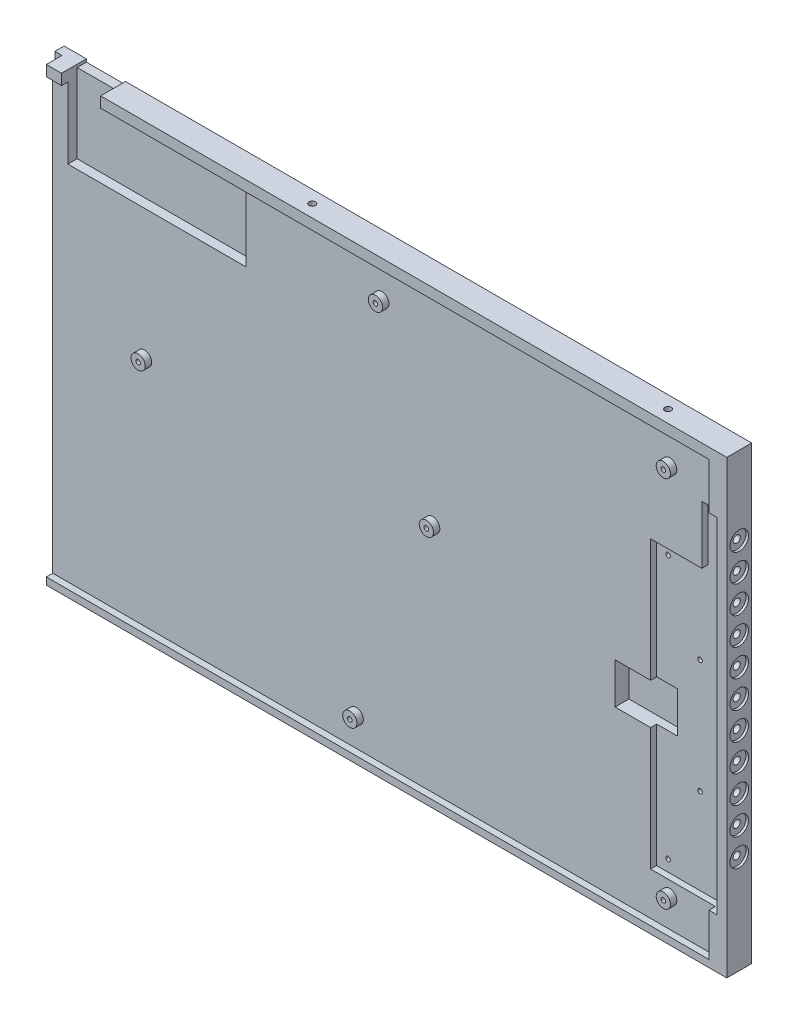
SolidWorks part; units mm, degrees
ref_plane "前视基准面" through (0, 0, 0) normal (0, 0, 1) x (1, 0, 0)
ref_plane "上视基准面" through (0, 0, 0) normal (0, 1, 0) x (1, 0, 0)
ref_plane "右视基准面" through (0, 0, 0) normal (1, 0, 0) x (0, 0, -1)
other "Configuration Table"
sketch "草图1" plane through (0, 0, 0) normal (0, 0, 1) x (1, 0, 0)
  line L1 (0, 0) -> (348.235, 0)
  line L2 (0, 0) -> (0, -124.71)
  line L3 (0, -124.71) -> (348.235, -124.71)
  line L4 (348.235, 0) -> (348.235, -124.71)
  dimension "D1" = 348.235
  dimension "D2" = 124.71
extrude "凸台-拉伸1" add sketch "草图1" along normal blind 7
sketch "草图2" plane through (0, 0, 7) normal (0, 0, 1) x (1, 0, 0)
  line L0 (348.235, 0) -> (0, 0) construction
  line L1 (2, -2) -> (346.235, -2)
  line L2 (2, -2) -> (2, -122.71)
  line L3 (2, -122.71) -> (346.235, -122.71)
  line L4 (346.235, -2) -> (346.235, -122.71)
  line L5 (348.235, -124.71) -> (348.235, 0) construction
  line L6 (0, -124.71) -> (348.235, -124.71) construction
  line L7 (0, 0) -> (0, -124.71) construction
  dimension "D1" = 2
  dimension "D2" = 2
  dimension "D3" = 2
  dimension "D4" = 2
extrude "切除-拉伸1" cut sketch "草图2" against normal blind 1.8
sketch "草图3" plane through (0, 0, 5.2) normal (0, 0, 1) x (1, 0, 0)
  circle A0 centre (4.8, -9.9) radius 2
  circle A1 centre (4.8, -9.9) radius 0.65
  circle A2 centre (7.2, -114.7) radius 2
  circle A3 centre (7.2, -114.7) radius 0.65
  circle A4 centre (76.2, -76.6) radius 2
  circle A5 centre (76.2, -76.6) radius 0.65
  circle A6 centre (128.6, -9.9) radius 2
  circle A7 centre (128.6, -9.9) radius 0.65
  circle A8 centre (126.3, -114.7) radius 2
  circle A9 centre (126.3, -114.7) radius 0.65
  circle A10 centre (185.8, -57.5) radius 2
  circle A11 centre (185.8, -57.5) radius 0.65
  circle A12 centre (252.5, -9.9) radius 2
  circle A13 centre (252.5, -9.9) radius 0.65
  circle A14 centre (245.3, -114.7) radius 2
  circle A15 centre (245.3, -114.7) radius 0.65
  circle A16 centre (333.4, -9.9) radius 2
  circle A17 centre (333.4, -9.9) radius 0.65
  circle A18 centre (333.4, -114.7) radius 2
  circle A19 centre (333.4, -114.7) radius 0.65
  circle A20 centre (266.8, -57.5) radius 2
  circle A21 centre (266.8, -57.5) radius 0.65
  dimension "D1" = 4
  dimension "D2" = 1.3
extrude "凸台-拉伸2" add sketch "草图3" along normal up to surface (1.8 mm away) up to face at (174.1175, -62.355, 7)
sketch "草图4" plane through (0, 0, 5.2) normal (0, 0, 1) x (1, 0, 0)
  line L0 (0, 0) -> (0, -124.71) construction
  line L1 (0, -27.51) -> (9.7, -27.51)
  line L2 (0, -27.51) -> (0, -107.91)
  line L3 (0, -107.91) -> (9.7, -107.91)
  line L4 (9.7, -27.51) -> (9.7, -107.91)
  line L5 (0, -124.71) -> (348.235, -124.71) construction
  dimension "D1" = 80.4
  dimension "D2" = 9.7
  dimension "D3" = 16.8
extrude "切除-拉伸2" cut sketch "草图4" against normal blind 1.7 and the other way through all contours L4 L3 L2 L1
sketch "草图6" plane through (0, 0, 5.2) normal (0, 0, 1) x (1, 0, 0)
  line L5 (3.9, -67.71) -> (9.7, -67.71) construction
  line L6 (3.9, -63.21) -> (19.7, -63.21)
  line L7 (3.9, -63.21) -> (3.9, -72.21)
  line L8 (3.9, -72.21) -> (19.7, -72.21)
  line L9 (19.7, -63.21) -> (19.7, -72.21)
  line L10 (9.7, -27.51) -> (9.7, -107.91) construction
  dimension "D1" = 9
  dimension "D2" = 5.8
  dimension "D3" = 10
extrude "切除-拉伸3" cut sketch "草图6" against normal offset from surface (3.9 mm away) 1.3 up to face at (174.1175, -62.355, 0)
sketch "草图7" plane through (0, 0, 0) normal (-1, 0, 0) x (0, 0, 1)
  line L1 (0, 0) -> (7, 0)
  line L2 (0, 0) -> (0, -27.51)
  line L3 (0, -27.51) -> (7, -27.51)
  line L4 (7, 0) -> (7, -27.51)
  line L5 (7, -107.91) -> (0, -107.91)
  line L6 (7, -107.91) -> (7, -124.71)
  line L7 (7, -124.71) -> (0, -124.71)
  line L8 (0, -107.91) -> (0, -124.71)
  line L9 (0, -107.91) -> (3.5, -107.91)
  line L10 (0, -107.91) -> (0, -27.51)
  line L11 (0, -27.51) -> (3.5, -27.51)
  line L12 (3.5, -107.91) -> (3.5, -27.51)
  line M1 (3.5, -107.91) -> (3.5, -27.51)
  line M2 (3.5, -27.51) -> (7, -27.51)
  line M3 (7, -27.51) -> (7, 0)
  line M4 (7, 0) -> (0, 0)
  line M5 (0, 0) -> (0, -124.71)
  line M6 (0, -124.71) -> (7, -124.71)
  line M7 (7, -124.71) -> (7, -107.91)
  line M8 (7, -107.91) -> (3.5, -107.91)
extrude "凸台-拉伸3" add sketch "草图7" along normal blind 11.7 contours L5 M8 M5 M6 M7 | L5 L3 M1 M5 | L3 M5 M2 M3 M4 region at (0, -13.755, 3.5) region at (0, -67.71, 1.75) region at (0, -116.31, 3.5)
sketch "草图8" plane through (0, 0, 3.5) normal (0, 0, 1) x (1, 0, 0)
  circle A0 centre (-5.5, -82.714) radius 0.7
  circle A1 centre (4.5, -102.714) radius 0.7
  circle A2 centre (-5.5, -52.714) radius 0.7
  circle A3 centre (4.5, -32.714) radius 0.7
  dimension "D1" = 1.4
extrude "切除-拉伸4" cut sketch "草图8" against normal blind 3
sketch "草图9" plane through (0, 0, 3.5) normal (0, 0, 1) x (1, 0, 0)
  line L0 (-11.7, -107.91) -> (2, -107.91) construction
  line L1 (-11.7, -27.51) -> (-10.7, -27.51)
  line L2 (-11.7, -27.51) -> (-11.7, -107.91)
  line L3 (-11.7, -107.91) -> (-10.7, -107.91)
  line L4 (-10.7, -27.51) -> (-10.7, -107.91)
  dimension "D1" = 1
extrude "凸台-拉伸4" add sketch "草图9" along normal up to surface (1.7 mm away) up to face at (64.8892, -65.925, 5.2)
sketch "草图10" plane through (0, 0, 5.2) normal (0, 0, 1) x (1, 0, 0)
  line L1 (328.035, -30.31) -> (348.235, -30.31)
  line L2 (328.035, -30.31) -> (328.035, -110.71)
  line L3 (328.035, -110.71) -> (348.235, -110.71)
  line L4 (348.235, -30.31) -> (348.235, -110.71)
  line L6 (348.235, -124.71) -> (348.235, 0) construction
  line L9 (2, -122.71) -> (346.235, -122.71) construction
  dimension "D1" = 80.4
  dimension "D2" = 20.2
  dimension "D3" = 12
extrude "切除-拉伸5" cut sketch "草图10" against normal blind 1.7 and the other way through all
sketch "草图11" plane through (0, 0, 3.5) normal (0, 0, 1) x (1, 0, 0)
  line L0 (328.035, -70.51) -> (333.835, -70.51) construction
  line L1 (318.035, -64.76) -> (333.835, -64.76)
  line L2 (318.035, -64.76) -> (318.035, -76.26)
  line L3 (318.035, -76.26) -> (333.835, -76.26)
  line L4 (333.835, -64.76) -> (333.835, -76.26)
  line L5 (328.035, -110.71) -> (328.035, -30.31) construction
  dimension "D1" = 11.5
  dimension "D2" = 5.8
  dimension "D3" = 10
extrude "切除-拉伸6" cut sketch "草图11" against normal blind 2.2 and the other way through all
sketch "草图12" plane through (0, 0, 3.5) normal (0, 0, 1) x (1, 0, 0)
  circle A3 centre (331.235, -107.514) radius 0.65
  circle A4 centre (340.235, -86.514) radius 0.65
  circle A5 centre (340.235, -54.514) radius 0.65
  circle A6 centre (331.235, -33.514) radius 0.65
  dimension "D1" = 1.3
extrude "切除-拉伸7" cut sketch "草图12" against normal blind 3
sketch "草图13" plane through (0, 0, 0) normal (0, 0, -1) x (-1, 0, 0)
  line L0 (11.7, -124.71) -> (-348.235, -124.71) construction
  line L1 (-348.235, 0) -> (-351.235, 0)
  line L2 (-348.235, 0) -> (-348.235, -124.71)
  line L3 (-348.235, -124.71) -> (-351.235, -124.71)
  line L4 (-351.235, 0) -> (-351.235, -124.71)
  dimension "D1" = 3
extrude "凸台-拉伸5" add sketch "草图13" against normal up to surface (7 mm away) up to face at (171.1925, -14.955, 7)
sketch "草图14" plane through (0, 0, 5.2) normal (0, 0, 1) x (1, 0, 0)
  line L0 (346.235, -2) -> (2, -2) construction
  line L1 (342.435, -14) -> (348.435, -14)
  line L2 (342.435, -14) -> (342.435, -110.71)
  line L3 (342.435, -110.71) -> (348.435, -110.71)
  line L4 (348.435, -14) -> (348.435, -110.71)
  line L5 (346.235, -110.71) -> (328.035, -110.71) construction
  line L6 (351.235, 0) -> (351.235, -124.71) construction
  dimension "D1" = 12
  dimension "D2" = 6
  dimension "D3" = 2.8
extrude "切除-拉伸8" cut sketch "草图14" against normal up to surface (1.7 mm away) and the other way blind 3 up to face at (340.885, -86.514, 3.5)
sketch "草图15" plane through (351.235, 0, 0) normal (1, 0, 0) x (0, 0, -1)
  line L0 (-7, 0) -> (0, 0) construction
  line L1 (-3.5, -20) -> (-3.5, 0)
  line L2 (-3.5, -104.71) -> (-3.5, -124.71)
  line L4 (-7, -124.71) -> (0, -124.71) construction
  circle A0 centre (-3.5, -20) radius 2.6
  circle A12 centre (-3.5, -20) radius 1
  circle A13 centre (-3.5, -27.7009) radius 2.6
  circle A14 centre (-3.5, -27.7009) radius 1
  circle A15 centre (-3.5, -35.4018) radius 2.6
  circle A16 centre (-3.5, -35.4018) radius 1
  circle A17 centre (-3.5, -43.1027) radius 2.6
  circle A18 centre (-3.5, -43.1027) radius 1
  circle A19 centre (-3.5, -50.8036) radius 2.6
  circle A20 centre (-3.5, -50.8036) radius 1
  circle A21 centre (-3.5, -58.5045) radius 2.6
  circle A22 centre (-3.5, -58.5045) radius 1
  circle A23 centre (-3.5, -66.2055) radius 2.6
  circle A24 centre (-3.5, -66.2055) radius 1
  circle A25 centre (-3.5, -73.9064) radius 2.6
  circle A26 centre (-3.5, -73.9064) radius 1
  circle A27 centre (-3.5, -81.6073) radius 2.6
  circle A28 centre (-3.5, -81.6073) radius 1
  circle A29 centre (-3.5, -89.3082) radius 2.6
  circle A30 centre (-3.5, -89.3082) radius 1
  circle A31 centre (-3.5, -97.0091) radius 2.6
  circle A32 centre (-3.5, -97.0091) radius 1
  circle A33 centre (-3.5, -104.71) radius 2.6
  circle A34 centre (-3.5, -104.71) radius 1
  point P5 (-3.5, 0)
  dimension "D2" = 5.2
  dimension "D3" = 2
  dimension "D1" = 20
  dimension "D4" = 12
extrude "切除-拉伸9" cut sketch "草图15" against normal blind 0.7 contours A0 | A13 | A15 | A17 | A19 | A21 | A23 | A25 | A27 | A29 | A31
extrude "切除-拉伸10" cut sketch "草图15<3>" against normal up to surface (2.8 mm away) contours A12 | A14 | A16 | A18 | A20 | A22 | A24 | A26 | A28 | A30 | A32 up to face at (348.435, -62.355, 5.25)
sketch "草图15<3>" plane through (351.235, 0, 0) normal (1, 0, 0) x (0, 0, -1) same geometry as "草图15"
sketch "草图16" plane through (0, 0, 0) normal (0, 1, 0) x (1, 0, 0)
  line L1 (-11.7, 0) -> (351.235, 0)
  line L2 (-11.7, 0) -> (-11.7, -7)
  line L3 (-11.7, -7) -> (351.235, -7)
  line L4 (351.235, 0) -> (351.235, -7)
extrude "凸台-拉伸6" add sketch "草图16" along normal blind 0.2
sketch "草图17" plane through (0, -124.71, 0) normal (0, -1, 0) x (1, 0, 0)
  line L1 (-11.7, 7) -> (351.235, 7)
  line L2 (-11.7, 7) -> (-11.7, 0)
  line L3 (-11.7, 0) -> (351.235, 0)
  line L4 (351.235, 7) -> (351.235, 0)
extrude "凸台-拉伸7" add sketch "草图17" along normal blind 0.2
sketch "草图23" plane through (0, 0, 0) normal (0, 0, -1) x (-1, 0, 0)
  line L0 (-351.235, 0.2) -> (-351.235, -124.91) construction
  line L1 (11.7, 0.2) -> (11.7, -124.91) construction
  line L2 (-351.235, 0.2) -> (11.7, 0.2) construction
  line L3 (11.7, -124.91) -> (-351.235, -124.91) construction
  circle A0 centre (-331.235, -19.8) radius 5.6
  circle A1 centre (-231.235, -19.8) radius 5.6
  circle A2 centre (-108.3, -19.8) radius 5.6
  circle A3 centre (-8.3, -19.8) radius 5.6
  circle A4 centre (-331.235, -104.91) radius 4.1
  circle A5 centre (-231.235, -104.91) radius 4.1
  circle A6 centre (-108.3, -104.91) radius 4.1
  circle A7 centre (-8.3, -104.91) radius 4.1
  dimension "D1" = 11.2
  dimension "D2" = 8.2
  dimension "D3" = 20
  dimension "D4" = 20
  dimension "D5" = 20
  dimension "D6" = 100
  dimension "D7" = 100
  dimension "D8" = 20
extrude "切除-拉伸14" cut sketch "草图23" against normal blind 1
sketch "草图24" plane through (0, 0.2, 0) normal (0, 1, 0) x (1, 0, 0)
  circle A0 centre (8.3, -3.5) radius 0.9
  circle A1 centre (108.3, -3.5) radius 0.9
  circle A2 centre (231.235, -3.5) radius 0.9
  circle A3 centre (331.235, -3.5) radius 0.9
  dimension "D1" = 1.8
sketch "草图25" plane through (0, 0.2, 0) normal (0, 1, 0) x (1, 0, 0)
  line L1 (-11.7, 0) -> (351.235, 0)
  line L2 (-11.7, 0) -> (-11.7, -7)
  line L3 (-11.7, -7) -> (351.235, -7)
  line L4 (351.235, 0) -> (351.235, -7)
extrude "凸台-拉伸8" add sketch "草图25" along normal blind 1.8
sketch "草图26" plane through (0, 0, 7) normal (0, 0, 1) x (1, 0, 0)
  line L0 (346.235, -14) -> (346.235, -2) construction
  line L1 (2, -2) -> (346.235, -2)
  line L2 (2, -2) -> (2, -1)
  line L3 (2, -1) -> (346.235, -1)
  line L4 (346.235, -2) -> (346.235, -1)
  dimension "D1" = 1
extrude "切除-拉伸15" cut sketch "草图26" against normal up to surface (1.8 mm away) up to face at (268.8, -57.5, 5.2)
sketch "草图27" plane through (0, 2, 0) normal (0, 1, 0) x (1, 0, 0)
  line L0 (351.235, 0) -> (-11.7, 0) construction
  line L1 (164.2675, 0) -> (175.2675, 0)
  line L2 (164.2675, 0) -> (164.2675, -7)
  line L3 (164.2675, -7) -> (175.2675, -7)
  line L4 (175.2675, 0) -> (175.2675, -7)
  line L5 (-11.7, -7) -> (351.235, -7) construction
  line L6 (164.2675, -4) -> (169.7675, -4) construction
  line L7 (169.7675, -4) -> (175.2675, -4) construction
  point P8 (169.7675, -4)
  dimension "D1" = 11
extrude "切除-拉伸16" cut sketch "草图27" against normal blind 0.8
sketch "草图28" plane through (0, 0, 5.2) normal (0, 0, 1) x (1, 0, 0)
  line L0 (346.235, -1) -> (2, -1) construction
  line L1 (164.2675, -1) -> (214.2675, -1)
  line L2 (164.2675, -1) -> (164.2675, -21)
  line L3 (164.2675, -21) -> (214.2675, -21)
  line L4 (214.2675, -1) -> (214.2675, -21)
  line L5 (164.2675, -1) -> (175.2675, -1)
  line L6 (164.2675, -1) -> (164.2675, 1.2)
  line L7 (164.2675, 1.2) -> (175.2675, 1.2)
  line L8 (175.2675, -1) -> (175.2675, 1.2)
  line L9 (164.2675, 1.2) -> (164.2675, 2) construction
  line M21 (346.235, -1) -> (2, -1)
  dimension "D1" = 20
  dimension "D2" = 50
extrude "切除-拉伸17" cut sketch "草图28" against normal blind 2.6 and the other way through all contours L4 L1 L2 L3 M21 | L1 L8 L7 L6 region at (169.7675, 0.1, 5.2) region at (189.2675, -11, 5.2)
sketch "草图29" plane through (-11.7, 0, 0) normal (-1, 0, 0) x (0, 0, 1)
  line L0 (0, 2) -> (0, -124.91) construction
  line L1 (7, -124.91) -> (0, -124.91)
  line L2 (7, -124.91) -> (7, -124.71)
  line L3 (7, -124.71) -> (0, -124.71)
  line L4 (0, -124.91) -> (0, -124.71)
  dimension "D1" = 0.2
extrude "切除-拉伸18" cut sketch "草图29" against normal through all
extrude "切除-拉伸19" cut sketch "草图24" against normal blind 2 from surface starting at face at (76.2837, 2, 3.5)
extrude "切除-拉伸20" cut sketch "草图24<3>" along normal blind 2 from surface starting at face at (169.7675, -124.71, 3.5)
sketch "草图24<3>" plane through (0, 0.2, 0) normal (0, 1, 0) x (1, 0, 0) same geometry as "草图24"
sketch "草图30" plane through (0, 0, 0) normal (0, 0, 1) x (1, 0, 0)
  line L1 (-87.4146, 53.5298) -> (160, 53.5298)
  line L2 (-87.4146, 53.5298) -> (-87.4146, -151.3065)
  line L3 (-87.4146, -151.3065) -> (160, -151.3065)
  line L4 (160, 53.5298) -> (160, -151.3065)
  dimension "D1" = 160
extrude "切除-拉伸21" cut sketch "草图30" against normal through all and the other way through all
sketch "草图31" plane through (160, 0, 0) normal (-1, 0, 0) x (0, 0, 1)
  line L0 (7, -124.71) -> (0, -124.71) construction
  line L1 (0, 2) -> (2.6, 2)
  line L2 (0, 2) -> (0, -124.71)
  line L3 (0, -124.71) -> (2.6, -124.71)
  line L4 (2.6, 2) -> (2.6, -124.71)
  line L5 (5.2, -61.855) -> (0, -61.855)
  line L6 (5.2, -122.71) -> (5.2, -1) construction
  point P11 (2.6, -61.855)
extrude "凸台-拉伸9" add sketch "草图31" along normal blind 2 contours L2 L3 L4 L1
